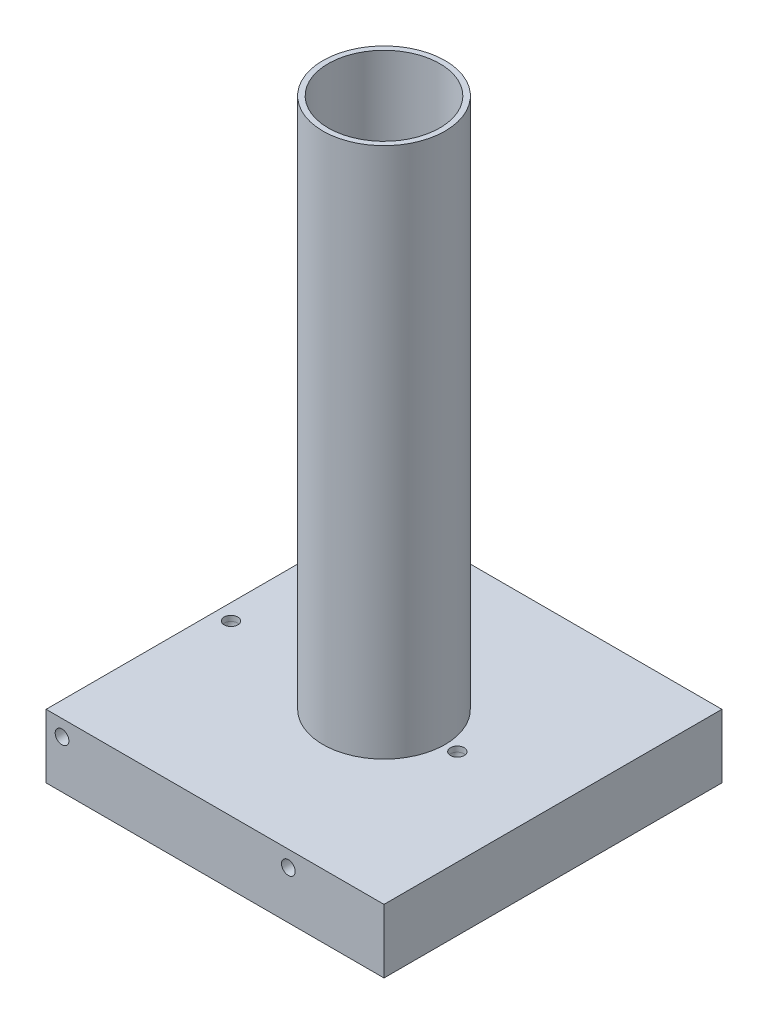
SolidWorks part; units mm, degrees
ref_plane "Front Plane" through (0, 0, 0) normal (0, 0, 1) x (1, 0, 0)
ref_plane "Top Plane" through (0, 0, 0) normal (0, 1, 0) x (1, 0, 0)
ref_plane "Right Plane" through (0, 0, 0) normal (1, 0, 0) x (0, 0, -1)
sketch "Sketch1" plane through (0, 0, 0) normal (0, 1, 0) x (1, 0, 0)
  line L1 (0, 0) -> (31.8, 0)
  line L2 (0, 0) -> (0, 31.8)
  line L3 (0, 31.8) -> (31.8, 31.8)
  line L4 (31.8, 0) -> (31.8, 31.8)
  dimension "D1" = 31.8
  dimension "D2" = 31.8
extrude "Boss-Extrude2" add sketch "Sketch1" against normal blind 6
sketch "Sketch5" plane through (0, -6, 0) normal (0, -1, 0) x (1, 0, 0)
  line L0 (19.6, -1.5) -> (19.6, -1.2)
  line L1 (30.6, -1.2) -> (1.2, -1.2)
  line L2 (30.6, -1.2) -> (30.6, -30.6)
  line L3 (30.6, -30.6) -> (1.2, -30.6)
  line L4 (1.2, -1.2) -> (1.2, -30.6)
  line L5 (31.8, 0) -> (31.8, -31.8) construction
  line L6 (3.3, 0) -> (-3.3, 0) construction
  line L7 (0, -3.3) -> (0, 3.3) construction
  line L8 (31.8, -31.8) -> (0, -31.8) construction
  line L9 (27.6, -1.5) -> (28.2, -1.5)
  line L10 (27.6, -1.5) -> (27.6, -1.2)
  line L11 (27.6, -1.2) -> (28.2, -1.2)
  line L12 (28.2, -1.5) -> (28.2, -1.2)
  line L13 (27.6, -1.5) -> (28.2, -1.2) construction
  line L14 (27.6, -1.2) -> (28.2, -1.5) construction
  line L15 (19.6, -1.5) -> (20.2, -1.5)
  line L16 (20.2, -1.5) -> (20.2, -1.2)
  line L17 (19.6, -1.2) -> (20.2, -1.2)
  line L18 (11.6, -1.5) -> (11.6, -1.2)
  line L19 (11.6, -1.5) -> (12.2, -1.5)
  line L20 (12.2, -1.5) -> (12.2, -1.2)
  line L21 (11.6, -1.2) -> (12.2, -1.2)
  line L22 (3.6, -1.5) -> (3.6, -1.2)
  line L23 (3.6, -1.5) -> (4.2, -1.5)
  line L24 (4.2, -1.5) -> (4.2, -1.2)
  line L25 (3.6, -1.2) -> (4.2, -1.2)
  line L26 (30.3, -27.6) -> (30.6, -27.6)
  line L27 (30.3, -27.6) -> (30.3, -28.2)
  line L28 (30.3, -28.2) -> (30.6, -28.2)
  line L29 (30.6, -27.6) -> (30.6, -28.2)
  line L30 (30.3, -19.6) -> (30.6, -19.6)
  line L31 (30.6, -19.6) -> (30.6, -20.2)
  line L32 (30.3, -20.2) -> (30.6, -20.2)
  line L33 (30.3, -19.6) -> (30.3, -20.2)
  line L34 (30.3, -11.6) -> (30.6, -11.6)
  line L35 (30.6, -11.6) -> (30.6, -12.2)
  line L36 (30.3, -12.2) -> (30.6, -12.2)
  line L37 (30.3, -11.6) -> (30.3, -12.2)
  line L38 (30.3, -3.6) -> (30.6, -3.6)
  line L39 (30.6, -3.6) -> (30.6, -4.2)
  line L40 (30.3, -4.2) -> (30.6, -4.2)
  line L41 (30.3, -3.6) -> (30.3, -4.2)
  line L42 (4.2, -30.3) -> (4.2, -30.6)
  line L43 (4.2, -30.3) -> (3.6, -30.3)
  line L44 (3.6, -30.3) -> (3.6, -30.6)
  line L45 (4.2, -30.6) -> (3.6, -30.6)
  line L46 (12.2, -30.3) -> (12.2, -30.6)
  line L47 (12.2, -30.6) -> (11.6, -30.6)
  line L48 (11.6, -30.3) -> (11.6, -30.6)
  line L49 (12.2, -30.3) -> (11.6, -30.3)
  line L50 (20.2, -30.3) -> (20.2, -30.6)
  line L51 (20.2, -30.6) -> (19.6, -30.6)
  line L52 (19.6, -30.3) -> (19.6, -30.6)
  line L53 (20.2, -30.3) -> (19.6, -30.3)
  line L54 (28.2, -30.3) -> (28.2, -30.6)
  line L55 (28.2, -30.6) -> (27.6, -30.6)
  line L56 (27.6, -30.3) -> (27.6, -30.6)
  line L57 (28.2, -30.3) -> (27.6, -30.3)
  line L58 (1.5, -4.2) -> (1.2, -4.2)
  line L59 (1.5, -4.2) -> (1.5, -3.6)
  line L60 (1.5, -3.6) -> (1.2, -3.6)
  line L61 (1.2, -4.2) -> (1.2, -3.6)
  line L62 (1.5, -12.2) -> (1.2, -12.2)
  line L63 (1.2, -12.2) -> (1.2, -11.6)
  line L64 (1.5, -11.6) -> (1.2, -11.6)
  line L65 (1.5, -12.2) -> (1.5, -11.6)
  line L66 (1.5, -20.2) -> (1.2, -20.2)
  line L67 (1.2, -20.2) -> (1.2, -19.6)
  line L68 (1.5, -19.6) -> (1.2, -19.6)
  line L69 (1.5, -20.2) -> (1.5, -19.6)
  line L70 (1.5, -28.2) -> (1.2, -28.2)
  line L71 (1.2, -28.2) -> (1.2, -27.6)
  line L72 (1.5, -27.6) -> (1.2, -27.6)
  line L73 (1.5, -28.2) -> (1.5, -27.6)
  circle A0 centre (23.9, -7.9) radius 2.4
  circle A1 centre (23.9, -7.9) radius 3.255
  circle A2 centre (15.9, -7.9) radius 2.4
  circle A3 centre (15.9, -7.9) radius 3.255
  circle A4 centre (7.9, -7.9) radius 2.4
  circle A5 centre (7.9, -7.9) radius 3.255
  circle A6 centre (15.9, -15.9) radius 2.4
  circle A7 centre (15.9, -15.9) radius 3.255
  circle A8 centre (7.9, -15.9) radius 2.4
  circle A9 centre (7.9, -15.9) radius 3.255
  circle A10 centre (15.9, -23.9) radius 2.4
  circle A11 centre (15.9, -23.9) radius 3.255
  circle A12 centre (7.9, -23.9) radius 2.4
  circle A13 centre (7.9, -23.9) radius 3.255
  circle A14 centre (23.9, -15.9) radius 2.4
  circle A15 centre (23.9, -15.9) radius 3.255
  circle A16 centre (23.9, -23.9) radius 2.4
  circle A17 centre (23.9, -23.9) radius 3.255
  point P16 (27.9, -1.35)
  point P107 (15.9, -15.9)
  dimension "D5" = 4.8
  dimension "D6" = 6.51
  dimension "D1" = 1.2
  dimension "D2" = 1.2
  dimension "D3" = 1.2
  dimension "D4" = 1.2
  dimension "D7" = 7.9
  dimension "D8" = 7.9
  dimension "D11" = 3.9
  dimension "D12" = 0.3
  dimension "D13" = 0.6
  dimension "D14" = 4
  dimension "D9" = 3
  dimension "D10" = 3
  dimension "D15" = 4
extrude "Cut-Extrude2" cut sketch "Sketch5" against normal blind 2 contours L1 L4 L3 L2 A17 A15 A13 A11 A9 A7 A5 A3 A1 | A0 | A14 | A16 | A10 | A6 | A2 | A4 | A8 | A12 region at (19.9, -6, -1.9158) region at (23.9, -6, -7.9) region at (15.9, -6, -7.9) region at (7.9, -6, -7.9) region at (15.9, -6, -15.9) region at (7.9, -6, -15.9) region at (15.9, -6, -23.9) region at (7.9, -6, -23.9) region at (23.9, -6, -15.9) region at (23.9, -6, -23.9)
sketch "Sketch6" plane through (0, 0, 0) normal (0, 1, 0) x (1, 0, 0)
  line L0 (31.8, 0) -> (31.8, 31.8) construction
  line L1 (0, 0) -> (31.8, 0) construction
  circle A0 centre (15.9, 15.9) radius 5
  dimension "D1" = 10
  dimension "D2" = 15.9
  dimension "D3" = 15.9
extrude "Cut-Extrude3" cut sketch "Sketch6" against normal blind 2
sketch "Sketch7" plane through (0, 0, 0) normal (0, 1, 0) x (1, 0, 0)
  circle A0 centre (15.9, 15.9) radius 5.25
  circle A1 centre (15.9, 15.9) radius 5.75
  dimension "D1" = 10.5
  dimension "D2" = 11.5
extrude "Boss-Extrude4" add sketch "Sketch7" along normal blind 50
ref_plane "Plane7" through (0, 0, -10.15) normal (0, 0, 1) x (1, 0, 0)
sketch "Sketch9" plane through (0, 0, -10.15) normal (0, 0, 1) x (1, 0, 0)
  line L0 (15.9, 50) -> (15.9, 49)
  line L1 (21.65, 50) -> (10.15, 50) construction
  line L2 (16.9, 50) -> (17.4, 49)
  line L3 (14.9, 48) -> (16.9, 48)
  line L4 (14.9, 48) -> (14.9, 50)
  line L5 (14.9, 50) -> (16.9, 50)
  line L6 (16.9, 48) -> (16.9, 50)
  line L7 (14.9, 48) -> (16.9, 50) construction
  line L8 (14.9, 50) -> (16.9, 48) construction
  line L9 (14.9, 49) -> (14.4, 49)
  line L10 (14.9, 49) -> (14.9, 50)
  line L13 (17.4, 49) -> (16.9, 49)
  line L16 (16.9, 49) -> (16.9, 50)
  line L17 (14.9, 50) -> (14.4, 49)
  dimension "D1" = 1
  dimension "D2" = 2
extrude "Boss-Extrude5" [suppressed] add sketch "Sketch9" along normal blind 1 and the other way blind 0.5 contours L4 L3 L6 L5 | L17 L9 L10 | L2 L13 L16
ref_axis "Axis1" through (15.9, 50, -15.9) along (0, -1, 0)
pattern_circular "CirPattern6" [suppressed] count 4 over 360 about axis through (15.9, 50, -15.9) along (0, -1, 0) of bodies 123 124
sketch "Sketch10" plane through (0, 0, 0) normal (0, 0, 1) x (1, 0, 0)
  line L1 (0, -6) -> (0, 0) construction
  line L2 (31.8, -6) -> (31.8, 0) construction
  line L3 (17.49, 0) -> (-17.49, 0) construction
  circle A0 centre (1.5, -1.5) radius 0.6452
  circle A1 centre (22.8, -1.5) radius 0.6452
  point P4 (0, 0)
  point P7 (0, 0)
  dimension "D1" = 1.2903
  dimension "D2" = 1.2903
  dimension "D3" = 1.5
  dimension "D4" = 9
  dimension "D5" = 1.5
  dimension "D6" = 1.5
ref_plane "Plane8" through (22.8, 0, 0) normal (1, 0, 0) x (0, 0, -1)
sketch "Sketch12" plane through (22.8, 0, 0) normal (1, 0, 0) x (0, 0, -1)
  line L0 (0, -1.5) -> (14.9, -1.5)
  line L1 (15.9, 0) -> (15.9, -0.5)
  line L2 (17.49, 0) -> (-17.49, 0) construction
  line L3 (15.9, 50) -> (15.9, 0) construction
  arc A0 (15.9, -0.5) -> (14.9, -1.5) centre (14.9, -0.5) cw
  point P3 (15.9, -1.5)
  point P10 (15.9, -1.3966)
  point P12 (15.9, -1.5)
  dimension "D1" = 1
sweep "Cut-Sweep1" cut profiles "Sketch10" path "Sketch12"
